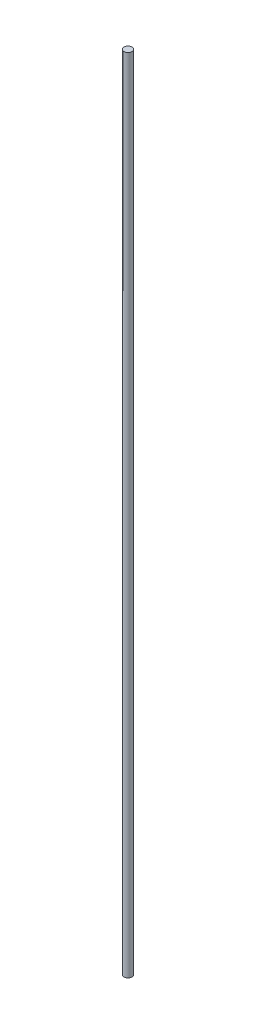
SolidWorks part; units mm, degrees
ref_plane "Front Plane" through (0, 0, 0) normal (0, 0, 1) x (1, 0, 0)
ref_plane "Top Plane" through (0, 0, 0) normal (0, 1, 0) x (1, 0, 0)
ref_plane "Right Plane" through (0, 0, 0) normal (1, 0, 0) x (0, 0, -1)
sketch "Sketch1" plane through (0, 0, 0) normal (0, 1, 0) x (1, 0, 0)
  circle A0 centre (0, 0) radius 5
extrude "Boss-Extrude1" add sketch "Sketch1" along normal blind 1000
